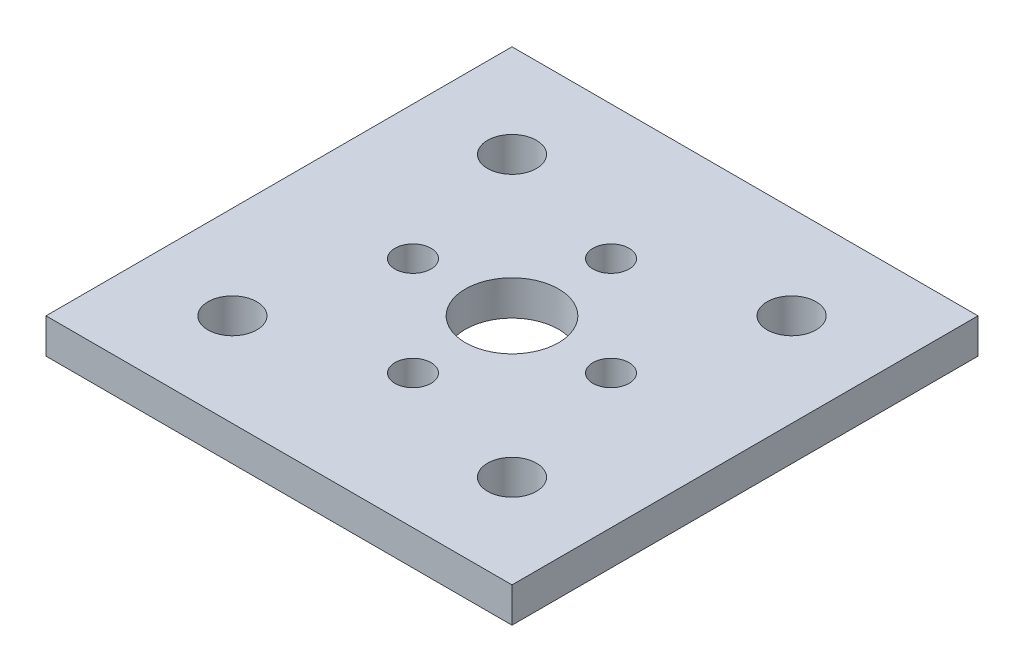
SolidWorks part; units mm, degrees
ref_plane "前视基准面" through (0, 0, 0) normal (0, 0, 1) x (1, 0, 0)
ref_plane "上视基准面" through (0, 0, 0) normal (0, 1, 0) x (1, 0, 0)
ref_plane "右视基准面" through (0, 0, 0) normal (1, 0, 0) x (0, 0, -1)
other "Configuration Table"
sketch "草图1" plane through (0, 0, 0) normal (0, 1, 0) x (1, 0, 0)
  line L0 (0, 8.5) -> (0, -8.5)
  line L1 (-20, 20) -> (20, 20)
  line L2 (-20, 20) -> (-20, -20)
  line L3 (-20, -20) -> (20, -20)
  line L4 (20, 20) -> (20, -20)
  line L5 (-20, 20) -> (20, -20) construction
  line L6 (-20, -20) -> (20, 20) construction
  line L7 (0, 0) -> (-20, 0) construction
  line L8 (-18.5, -18.5) -> (18.5, -18.5)
  line L9 (18.5, 18.5) -> (18.5, -18.5)
  line L10 (-18.5, 18.5) -> (18.5, 18.5)
  line L11 (-18.5, 18.5) -> (-18.5, -18.5)
  circle A0 centre (0, 0) radius 12.6
  circle A1 centre (0, 8.5) radius 1.55
  circle A3 centre (0, 0) radius 4
  circle A4 centre (8.5, 0) radius 1.55
  circle A5 centre (0, -8.5) radius 1.55
  circle A6 centre (-8.5, 0) radius 1.55
  point P0 (0, 0)
  point P11 (0, 0)
  point P23 (0, 0)
  dimension "D4" = 25.2
  dimension "D6" = 3.1
  dimension "D7" = 8
  dimension "D8" = 4
  dimension "D1" = 40
  dimension "D2" = 40
  dimension "D3" = 20
  dimension "D5" = 17
  dimension "D10" = 1.5
  dimension "D9" = 1.5
extrude "凸台-拉伸2" add sketch "草图1" against normal blind 3 contours L2 L3 L4 L1 | A6 | A5 | A1 | A4
extrude "切除-拉伸1" cut sketch "草图1<6>" against normal blind 1.5 contours L0 A3 | L0 A3 region at (1.6977, 0, 0) region at (-1.6977, 0, 0)
sketch "草图1<6>" plane through (0, 0, 0) normal (0, 1, 0) x (1, 0, 0) same geometry as "草图1"
sketch "草图2" plane through (0, 0, 0) normal (0, 1, 0) x (1, 0, 0)
  line L0 (-20, -20) -> (20, -20) construction
  line L1 (20, 20) -> (20, -20) construction
  line L2 (-20, 20) -> (-20, -20) construction
  line L3 (-20, 20) -> (20, 20) construction
  line L4 (-20, -20) -> (20, -20)
  line L5 (20, 20) -> (20, -20)
  line L6 (-20, 20) -> (-20, -20)
  line L7 (-20, 20) -> (20, 20)
  line L8 (0, 0) -> (38.7801, 0) construction
  line L9 (-20, 20) -> (-17, 20)
  line L10 (-20, 20) -> (-20, 17)
  line L11 (-20, 17) -> (-17, 17)
  line L12 (-17, 20) -> (-17, 17)
  line L13 (0, 0) -> (0, 17.8693) construction
  line L14 (20, -17) -> (17, -17)
  line L15 (20, 20) -> (17, 20)
  line L16 (20, 20) -> (20, 17)
  line L17 (20, 17) -> (17, 17)
  line L18 (17, 20) -> (17, 17)
  line L19 (17, -20) -> (17, -17)
  line L20 (20, -20) -> (17, -20)
  line L21 (20, -20) -> (20, -17)
  line L22 (-20, -20) -> (-20, -17)
  line L23 (-20, -20) -> (-17, -20)
  line L24 (-17, -20) -> (-17, -17)
  line L25 (-20, -17) -> (-17, -17)
  circle A0 centre (0, -8.5) radius 1.55 construction
  circle A1 centre (8.5, 0) radius 1.55 construction
  circle A2 centre (0, 8.5) radius 1.55 construction
  circle A3 centre (0, 0) radius 4 construction
  circle A4 centre (-8.5, 0) radius 1.55 construction
  circle A5 centre (0, -8.5) radius 1.55
  circle A6 centre (8.5, 0) radius 1.55
  circle A7 centre (0, 8.5) radius 1.55
  circle A8 centre (0, 0) radius 4
  circle A9 centre (-8.5, 0) radius 1.55
  point P35 (18.5, -17)
  line M9 (20, 20) -> (-20, 20)
  line M10 (-20, 20) -> (-20, -20)
  line M11 (-20, -20) -> (20, -20)
  line M12 (20, -20) -> (20, 20)
  dimension "D1" = 3
  dimension "D2" = 3
  dimension "D3" = 34
  dimension "D4" = 34
  dimension "D5" = 34
  dimension "D6" = 34
extrude "凸台-拉伸7" add sketch "草图2" along normal blind 45 contours L12 L7 L11 M10 | L18 L17 M9 M12 | L19 L4 L14 M12 | L25 L24 M10 M11 region at (-18.5, 0, 18.5) region at (18.5, 0, 18.5) region at (-18.5, 0, -18.5) region at (18.5, 0, -18.5)
sketch "草图5" plane through (-20, 0, 0) normal (-1, 0, 0) x (0, 0, 1)
  line L0 (20, -3) -> (20, 45) construction
  line L1 (-20, -3) -> (-20, 45) construction
  line L2 (20, -3) -> (20, 45)
  line L3 (-20, -3) -> (-20, 45)
  line L4 (-17, 0) -> (-17, 45)
  line L5 (-17, 45) -> (-17, 0) construction
  line L7 (-20, 45) -> (20, 45)
  line L8 (-20, 45) -> (-20, 42)
  line L9 (-20, 42) -> (20, 42)
  line L10 (20, 45) -> (20, 42)
extrude "凸台-拉伸8" add sketch "草图5" against normal blind 40 contours L8 L9 L10 L7
sketch "草图6" plane through (0, 45, 0) normal (0, 1, 0) x (1, 0, 0)
  line L0 (-20, -20) -> (0, -20)
  line L1 (0, -20) -> (0, 0)
  line L4 (20, -20) -> (20, 20)
  line L5 (20, 20) -> (-20, 20)
  line L6 (-20, 20) -> (-20, -20)
  line L7 (-20, -20) -> (20, -20)
  line L8 (20, -20) -> (20, 20)
  line L9 (20, 20) -> (-20, 20)
  line L10 (-20, 20) -> (-20, -20)
  line L11 (-20, -20) -> (20, -20)
  circle A0 centre (0, 0) radius 12.5
  dimension "D1" = 0
extrude "切除-拉伸2" cut sketch "草图6" against normal blind 4 contours A0 region at (-8.5888, 45, -8.5888)
sketch "草图7" plane through (0, -3, 0) normal (0, -1, 0) x (1, 0, 0)
  line L1 (-20, -20) -> (0, -20)
  line L2 (-20, -20) -> (-20, 0)
  line L3 (-20, 0) -> (0, 0)
  line L4 (-20, -20) -> (20, -20)
  line L5 (20, -20) -> (20, 20)
  line L6 (20, 20) -> (-20, 20)
  line L7 (-20, 20) -> (-20, -20)
  line L8 (-20, -20) -> (20, -20)
  line L9 (20, -20) -> (20, 20)
  line L10 (20, 20) -> (-20, 20)
  line L11 (-20, 20) -> (-20, -20)
  line L12 (0, -20) -> (0, 0)
  circle A0 centre (0, 0) radius 4
  dimension "D1" = 0
extrude "切除-拉伸3" cut sketch "草图7" against normal blind 4 contours L12 A0 L3 | L3 A0 L12 region at (-1.6977, -3, -1.6977) region at (0.5659, -3, 0.5659)
sketch "草图8" plane through (0, -3, 0) normal (0, -1, 0) x (1, 0, 0)
  line L0 (-20, 20) -> (0, 0) construction
  line L1 (0, 0) -> (20, 20) construction
  line L2 (-20, -20) -> (-20, 20) construction
  circle A0 centre (-12, 12) radius 5
  circle A1 centre (12, 12) radius 5
  circle A2 centre (12, -12) radius 5
  circle A3 centre (-12, -12) radius 5
  point P19 (0, 0)
  dimension "D1" = 8
  dimension "D2" = 4
extrude "切除-拉伸4" cut sketch "草图8" against normal blind 4
sketch "草图9" plane through (0, 45, 0) normal (0, 1, 0) x (1, 0, 0)
  line L0 (-20, 20) -> (0, 0) construction
  line L1 (0, 0) -> (20, 20) construction
  line L4 (20, -20) -> (20, 20)
  line L5 (20, 20) -> (-20, 20)
  line L6 (-20, 20) -> (-20, -20)
  line L7 (-20, -20) -> (20, -20)
  line L8 (20, -20) -> (20, 20)
  line L9 (20, 20) -> (-20, 20)
  line L10 (-20, 20) -> (-20, -20)
  line L11 (-20, -20) -> (20, -20)
  circle A0 centre (-12.7279, 12.7279) radius 2.5
  circle A1 centre (0, 0) radius 12.5 construction
  circle A2 centre (12.7279, 12.7279) radius 2.5
  circle A3 centre (12.7279, -12.7279) radius 2.5
  circle A4 centre (-12.7279, -12.7279) radius 2.5
  point P19 (0, 0)
  dimension "D2" = 18
  dimension "D3" = 4
  dimension "D1" = 0
extrude "切除-拉伸5" cut sketch "草图9" against normal blind 4 contours A0 | A4 | A2 | A3
sketch "草图10" plane through (0, 0, 0) normal (0, 1, 0) x (1, 0, 0)
  line L0 (20, -17) -> (17, -17) construction
  line L1 (20, 17) -> (18.5, 17)
  line L2 (20, 17) -> (20, -17)
  line L3 (20, -17) -> (18.5, -17)
  line L4 (18.5, 17) -> (18.5, -17)
  line L5 (17, -20) -> (-17, -20)
  line L6 (17, -20) -> (17, -18.5)
  line L7 (17, -18.5) -> (-17, -18.5)
  line L8 (-17, -20) -> (-17, -18.5)
  line L9 (-20, -17) -> (-20, 17)
  line L10 (-20, -17) -> (-18.5, -17)
  line L11 (-18.5, -17) -> (-18.5, 17)
  line L12 (-20, 17) -> (-18.5, 17)
  line L13 (-17, 20) -> (17, 20)
  line L14 (-17, 20) -> (-17, 18.5)
  line L15 (-17, 18.5) -> (17, 18.5)
  line L16 (17, 20) -> (17, 18.5)
  point P25 (0, 0)
  dimension "D1" = 4
extrude "凸台-拉伸10" add sketch "草图10" along normal blind 45
sketch "草图20" plane through (0, 0, 18.5) normal (0, 0, -1) x (-1, 0, 0)
  line L0 (0, 0) -> (0, 42)
  line L1 (-17, 0) -> (17, 0) construction
  line L2 (-20, -3) -> (-20, 45) construction
  line L3 (0, 0) -> (0, 3)
  line L4 (0, 3) -> (0, 5.5)
  line L5 (0, 21) -> (4.1437, 21)
  line L6 (-2.45, 36.5) -> (-2.45, 5.5)
  line L7 (2.45, 36.5) -> (2.45, 5.5)
  line L8 (-20, 45) -> (20, 45) construction
  line L9 (20, -3) -> (-20, -3) construction
  arc A1 (-2.45, 5.5) -> (2.45, 5.5) centre (0, 5.5) ccw
  arc A2 (-2.45, 36.5) -> (2.45, 36.5) centre (0, 36.5) cw
  point P10 (0, 45)
  point P13 (0, 38.95)
  point P20 (0, -3)
  point P21 (0, 3)
  dimension "D1" = 90
  dimension "D3" = 2.45
  dimension "D2" = 20
  dimension "D4" = 5.5
extrude "切除-拉伸12" cut sketch "草图20" against normal blind 4 and the other way through all contours L7 A1 L6 A2
sketch "草图24" plane through (20, 0, 0) normal (1, 0, 0) x (0, 0, -1)
  line L0 (0, -3) -> (0, 3)
  line L1 (0, 21) -> (-20, 21) construction
  line L2 (20, -3) -> (-20, -3) construction
  line L3 (0, 3) -> (0, 5.5)
  line L4 (0, -3) -> (0, 0)
  line L5 (0, 0) -> (0, 42)
  line L6 (0, 21) -> (5.4047, 21)
  line L7 (-2.45, 36.5) -> (-2.45, 5.5)
  line L8 (2.45, 5.5) -> (2.45, 36.5)
  line L9 (-20, 45) -> (20, 45) construction
  line L12 (-11.35, -3) -> (-11.35, 45) construction
  line L13 (-11.35, 21) -> (-11.35, 49) construction
  line L16 (20, -3) -> (20, 45)
  line L17 (20, 45) -> (-20, 45)
  line L18 (-20, 45) -> (-20, -3)
  line L19 (-20, -3) -> (20, -3)
  line L20 (20, -3) -> (20, 45)
  line L21 (20, 45) -> (-20, 45)
  line L22 (-20, 45) -> (-20, -3)
  line L23 (-20, -3) -> (20, -3)
  arc A0 (-2.45, 5.5) -> (2.45, 5.5) centre (0, 5.5) ccw
  arc A1 (-2.45, 36.5) -> (2.45, 36.5) centre (0, 36.5) cw
  circle A2 centre (-11.45, 35) radius 1.85
  circle A3 centre (-11.45, 7) radius 1.85
  circle A4 centre (11.45, 7) radius 1.85
  circle A5 centre (11.45, 35) radius 1.85
  circle A6 centre (-11.35, 21) radius 5.5
  circle A7 centre (11.35, 21) radius 5.5
  point P7 (0, 38.95)
  point P13 (0, 45)
  point P18 (0, 3.05)
  point P37 (-11.45, 35)
  dimension "D1" = 3
  dimension "D3" = 9
  dimension "D4" = 3.7
  dimension "D6" = 10
  dimension "D7" = 8.65
  dimension "D8" = 2.45
  dimension "D2" = 8.5
  dimension "D5" = 0
extrude "切除-拉伸13" cut sketch "草图24" along normal blind 4 and the other way through all contours L7 A0 L8 A1
extrude "切除-拉伸15" cut sketch "草图24<5>" along normal blind 10 and the other way through all contours A2 | A5 | A6 | A7 | A3 | A4
sketch "草图24<5>" plane through (20, 0, 0) normal (1, 0, 0) x (0, 0, -1) same geometry as "草图24"
sketch "草图25" plane through (0, 0, -20) normal (0, 0, -1) x (-1, 0, 0)
  line L0 (-11.45, -3) -> (-11.45, 45) construction
  line L1 (-2.45, 36.5) -> (-2.45, 5.5) construction
  line L2 (-11.45, 21) -> (-31.2071, 21) construction
  line L3 (-11.45, 45) -> (-11.45, 35) construction
  line L4 (20, -3) -> (20, 45)
  line L5 (20, 45) -> (-20, 45)
  line L6 (-20, 45) -> (-20, -3)
  line L7 (-20, -3) -> (20, -3)
  line L8 (20, -3) -> (20, 45)
  line L9 (20, 45) -> (-20, 45)
  line L10 (-20, 45) -> (-20, -3)
  line L11 (-20, -3) -> (20, -3)
  line L12 (0, 0) -> (0, 45) construction
  line L13 (-2.45, 36.5) -> (-2.45, 5.5)
  circle A0 centre (-11.45, 21) radius 5.5
  circle A1 centre (-11.45, 35) radius 1.85
  circle A2 centre (11.45, 35) radius 1.85
  circle A3 centre (11.45, 7) radius 1.85
  circle A4 centre (-11.45, 7) radius 1.85
  circle A5 centre (11.45, 21) radius 5.5
  dimension "D3" = 10
  dimension "D4" = 11
  dimension "D2" = 9
  dimension "D1" = 0
extrude "切除-拉伸16" cut sketch "草图25" along normal blind 10 and the other way through all contours A0 | A5 | A1 | A4 | A3 | A2 region at (11.45, 21, -20) region at (-11.45, 21, -20)
sketch "草图26" plane through (0, 0, 0) normal (0, 1, 0) x (1, 0, 0)
  line L1 (-20, -20) -> (20, -20)
  line L2 (-20, -20) -> (-20, 20)
  line L3 (-20, 20) -> (20, 20)
  line L4 (20, -20) -> (20, 20)
extrude "切除-拉伸17" cut sketch "草图26" along normal through all
sketch "草图27" plane through (0, 0, 0) normal (0, 1, 0) x (1, 0, 0)
  circle A0 centre (-12, 12) radius 5
  circle A1 centre (12, 12) radius 5
  circle A2 centre (-12, -12) radius 5
  circle A3 centre (12, -12) radius 5
  circle A4 centre (-12, -12) radius 2.1
  circle A5 centre (-12, 12) radius 2.1
  circle A6 centre (12, 12) radius 2.1
  circle A7 centre (12, -12) radius 2.1
  dimension "D1" = 4.2
  dimension "D2" = 4.2
  dimension "D3" = 4.2
  dimension "D4" = 4.2
extrude "凸台-拉伸12" add sketch "草图27" against normal blind 3
